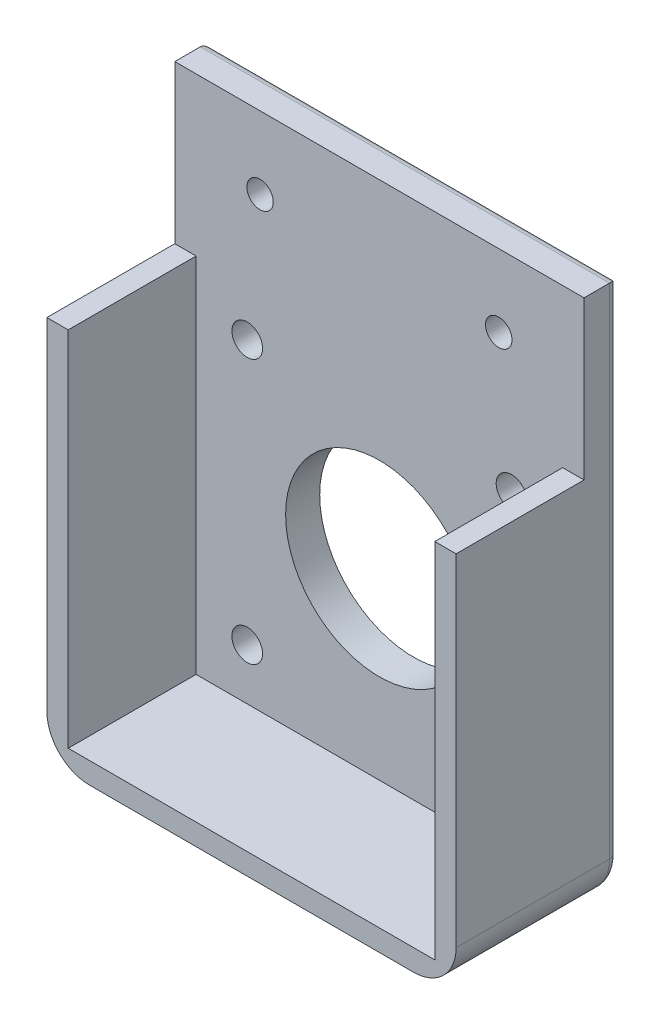
SolidWorks part; units mm, degrees
ref_plane "Plan de face" through (0, 0, 0) normal (0, 0, 1) x (1, 0, 0)
ref_plane "Plan de dessus" through (0, 0, 0) normal (0, 1, 0) x (1, 0, 0)
ref_plane "Plan de droite" through (0, 0, 0) normal (1, 0, 0) x (0, 0, -1)
sketch "Esquisse1" plane through (0, 0, 0) normal (0, 0, 1) x (1, 0, 0)
  line L1 (-14.3544, 68.9741) -> (33.6456, 68.9741)
  line L2 (-14.3544, 68.9741) -> (-14.3544, 5.4741)
  line L3 (-14.3544, 5.4741) -> (33.6456, 5.4741)
  line L4 (33.6456, 68.9741) -> (33.6456, 5.4741)
  dimension "D1" = 63.5
  dimension "D2" = 48
extrude "Boss.-Extru.1" add sketch "Esquisse1" along normal blind 4
fillet "Congé1" radius 1 4 edges at (9.6456, 5.4741, 0) (-14.3544, 37.2241, 0) (33.6456, 37.2241, 0) (9.6456, 68.9741, 0)
sketch "Esquisse2" plane through (0, 0, 4) normal (0, 0, 1) x (1, 0, 0)
  line L0 (9.6456, 5.4741) -> (9.6456, 29.4741)
  line L1 (-14.3544, 5.4741) -> (33.6456, 5.4741) construction
  dimension "D1" = 24
sketch "Esquisse3" plane through (0, 0, 4) normal (0, 0, 1) x (1, 0, 0)
  point P0 (9.6456, 29.4741)
hole_wizard "Diamètre du perçage Ø22.0 (22)1" positions "Esquisse3" profile "Esquisse4" hole size "Ø22.0" standard "ISO" end condition through all
sketch "Esquisse4" plane through (9.6456, 29.4741, 4) normal (1, 0, 0) x (0, -1, 0)
  line L0 (0, 0) -> (0, 4)
  line L1 (0, 4) -> (11, 4)
  line L2 (11, 4) -> (11, 0)
  line L5 (11, 0) -> (0, 0)
  line L11 (0, -6.35) -> (0, 107.95) construction
  dimension "Diamètre du perçage jusqu'au prochain" = 22
  dimension "Profondeur du perçage jusqu'au prochain" = 4
sketch "Esquisse5" plane through (0, 0, 0) normal (0, 0, 1) x (1, 0, 0)
  line L0 (9.6456, 29.4741) -> (9.6456, 44.9741)
  line L1 (9.6456, 44.9741) -> (-5.8544, 44.9741)
  dimension "D1" = 15.5
  dimension "D2" = 15.5
sketch "Esquisse6" plane through (0, 0, 4) normal (0, 0, 1) x (1, 0, 0)
  point P0 (-5.8544, 44.9741)
hole_wizard "Dégagement M31" positions "Esquisse6" profile "Esquisse7" hole size "M3" standard "ISO" end condition through all
sketch "Esquisse7" plane through (-5.8544, 44.9741, 4) normal (1, 0, 0) x (0, -1, 0)
  line L0 (0, 0) -> (0, 4)
  line L1 (0, 4) -> (1.8, 4)
  line L2 (1.8, 4) -> (1.8, 0)
  line L5 (1.8, 0) -> (0, 0)
  line L11 (0, -6.35) -> (0, 107.95) construction
  dimension "Diamètre du perçage jusqu'au prochain" = 3.6
  dimension "Profondeur du perçage jusqu'au prochain" = 4
pattern_linear "Répétition linéaire1" count 2 spacing 31 along (1, 0, 0) of "Dégagement M31"
pattern_linear "Répétition linéaire2" count 2 spacing 31 along (0, -1, 0) of "Répétition linéaire1"
sketch "Esquisse10" plane through (0, 0, 4) normal (0, 0, 1) x (1, 0, 0)
  line L0 (9.6456, 68.9741) -> (9.6456, 60.4741) construction
  line L1 (33.6456, 68.9741) -> (-14.3544, 68.9741) construction
  line L2 (-14.3544, 60.4741) -> (-4.3544, 60.4741) construction
  line L3 (-14.3544, 68.9741) -> (-14.3544, 5.4741) construction
  line L5 (33.6456, 60.4741) -> (23.6456, 60.4741) construction
  line L6 (33.6456, 5.4741) -> (33.6456, 68.9741) construction
  point P17 (0, 0)
  dimension "D1" = 8.5
  dimension "D2" = 10
  dimension "D3" = 10
sketch "Esquisse16" plane through (0, 0, 4) normal (0, 0, 1) x (1, 0, 0)
  point P0 (-4.3544, 60.4741)
  point P3 (23.6456, 60.4741)
hole_wizard "Dégagement M2.54" positions "Esquisse16" profile "Esquisse17" hole size "M2.5" standard "ISO" end condition through all
sketch "Esquisse17" plane through (-4.3544, 60.4741, 4) normal (1, 0, 0) x (0, -1, 0)
  line L0 (0, 0) -> (0, 4)
  line L1 (0, 4) -> (1.55, 4)
  line L2 (1.55, 4) -> (1.55, 0)
  line L5 (1.55, 0) -> (0, 0)
  line L11 (0, -6.35) -> (0, 107.95) construction
  dimension "Diamètre du perçage jusqu'au prochain" = 3.1
  dimension "Profondeur du perçage jusqu'au prochain" = 4
sketch "Esquisse19" plane through (0, 0, 4) normal (0, 0, 1) x (1, 0, 0)
  line L1 (-14.3544, 5.4741) -> (-11.8544, 5.4741)
  line L2 (-14.3544, 5.4741) -> (-14.3544, 50.4741)
  line L3 (-14.3544, 50.4741) -> (-11.8544, 50.4741)
  line L4 (-11.8544, 5.4741) -> (-11.8544, 50.4741)
  line L5 (33.6456, 5.4741) -> (31.1456, 5.4741)
  line L6 (33.6456, 5.4741) -> (33.6456, 50.4741)
  line L7 (33.6456, 50.4741) -> (31.1456, 50.4741)
  line L8 (31.1456, 5.4741) -> (31.1456, 50.4741)
  line L9 (-11.8544, 5.4741) -> (31.1456, 5.4741)
  line L10 (-11.8544, 5.4741) -> (-11.8544, 7.9741)
  line L11 (-11.8544, 7.9741) -> (31.1456, 7.9741)
  line L12 (31.1456, 5.4741) -> (31.1456, 7.9741)
  line L15 (6.5557, 7.9741) -> (6.5557, 5.4741) construction
  line M21 (-14.3544, 68.9741) -> (-14.3544, 5.4741)
  line M22 (-14.3544, 5.4741) -> (33.6456, 5.4741)
  line M23 (33.6456, 5.4741) -> (33.6456, 68.9741)
  dimension "D1" = 2.5
  dimension "D2" = 2.5
  dimension "D3" = 45
  dimension "D4" = 45
  dimension "D5" = 2.5
extrude "Boss.-Extru.2" add sketch "Esquisse19" along normal blind 15 contours L4 L3 M22 M21 | L15 L11 L4 M22 | L11 L15 L9 L8 | L8 L7 M22 M23 region at (-13.1044, 27.9741, 4) region at (-2.6494, 6.7241, 4) region at (18.8506, 6.7241, 4) region at (32.3956, 27.9741, 4)
fillet "Congé2" radius 5 4 edges at (-14.0615, 5.767, 0.2929) (33.3527, 5.767, 0.2929) (33.6456, 5.4741, 10) (-14.3544, 5.4741, 10)
